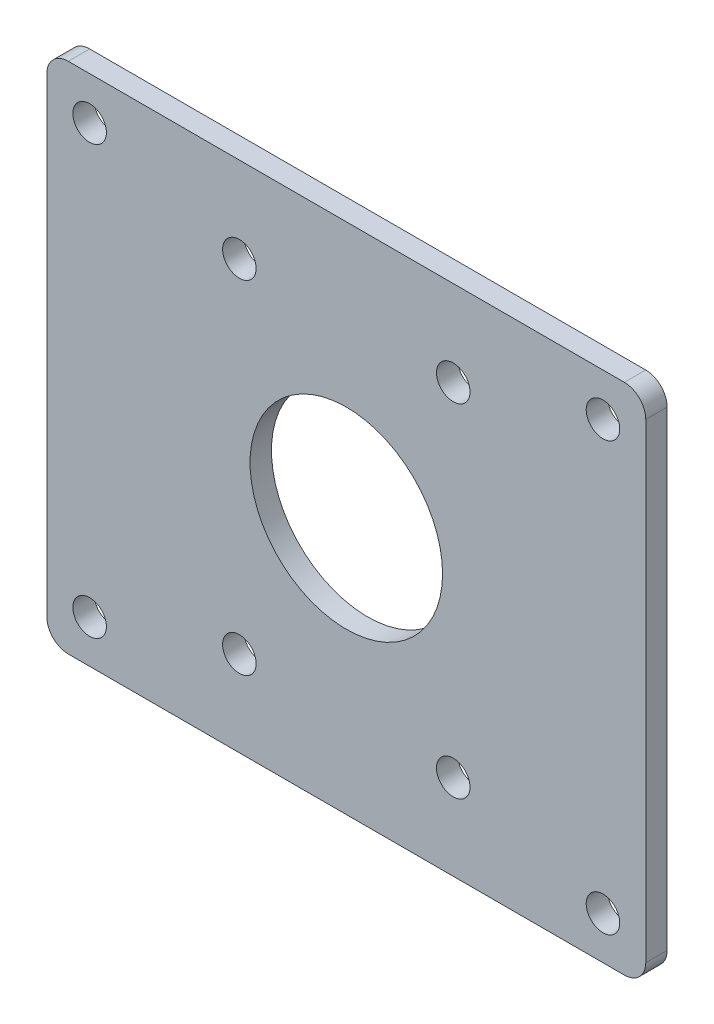
SolidWorks part; units mm, degrees
material "6061-T6 (SS)"
ref_plane "Front Plane" through (0, 0, 0) normal (0, 0, 1) x (1, 0, 0)
ref_plane "Top Plane" through (0, 0, 0) normal (0, 1, 0) x (1, 0, 0)
ref_plane "Right Plane" through (0, 0, 0) normal (1, 0, 0) x (0, 0, -1)
sketch "Sketch1" plane through (0, 0, 0) normal (0, 0, 1) x (1, 0, 0)
  line L8 (-38.1, -31.75) -> (-38.1, 31.75) construction
  line L9 (-44.45, -38.1) -> (44.45, -38.1)
  line L10 (-44.45, -38.1) -> (-44.45, 38.1)
  line L11 (-44.45, 38.1) -> (44.45, 38.1)
  line L12 (44.45, -38.1) -> (44.45, 38.1)
  line L13 (-44.45, -38.1) -> (44.45, 38.1) construction
  line L14 (-44.45, 38.1) -> (44.45, -38.1) construction
  line L19 (-37.0417, -31.75) -> (37.0417, 31.75) construction
  line L20 (-59.6943, 51.1665) -> (37.0417, -31.75) construction
  line L21 (-25.4, -38.1) -> (25.4, -38.1) construction
  line L22 (-25.4, -38.1) -> (-25.4, 38.1) construction
  line L23 (-25.4, 38.1) -> (25.4, 38.1) construction
  line L24 (25.4, -38.1) -> (25.4, 38.1) construction
  line L25 (-25.4, -38.1) -> (25.4, 38.1) construction
  line L26 (-25.4, 38.1) -> (25.4, -38.1) construction
  line L27 (-38.1, 31.75) -> (38.1, 31.75) construction
  line L28 (38.1, -31.75) -> (38.1, 31.75) construction
  line L29 (-38.1, -31.75) -> (38.1, -31.75) construction
  circle A8 centre (0, 0) radius 30 construction
  circle A9 centre (0, 0) radius 14.2875
  circle A11 centre (0, 0) radius 9.5758 construction
  circle A12 centre (0, 0) radius 11.5062 construction
  circle A13 centre (-15.875, -25.4) radius 2.4892
  circle A14 centre (15.875, -25.4) radius 2.4892
  circle A15 centre (15.875, 25.4) radius 2.4892
  circle A16 centre (-15.875, 25.4) radius 2.4892
  circle A17 centre (-38.1, 31.75) radius 2.4892
  circle A21 centre (-38.1, -31.75) radius 2.4892
  circle A22 centre (38.1, -31.75) radius 2.4892
  circle A23 centre (38.1, 31.75) radius 2.4892
  point P0 (0, 0)
  point P6 (0, 0)
  dimension "D4" = 28.575
  dimension "D3" = 4.9784
  dimension "D5" = 60
  dimension "D7" = 19.1516
  dimension "D8" = 23.0124
  dimension "D10" = 2
  dimension "D11" = 31.75
  dimension "D12" = 50.8
  dimension "D1" = 88.9
  dimension "D2" = 6.35
  dimension "D6" = 50.8
  dimension "D9" = 2
  dimension "D13" = 15.875
  dimension "D14" = 25.4
  dimension "D15" = 76.2
extrude "Boss-Extrude1" add sketch "Sketch1" along normal blind 3.175
fillet "Fillet1" radius 3.175 4 edges at (44.45, -38.1, 1.5875) (-44.45, -38.1, 1.5875) (-44.45, 38.1, 1.5875) (44.45, 38.1, 1.5875)
